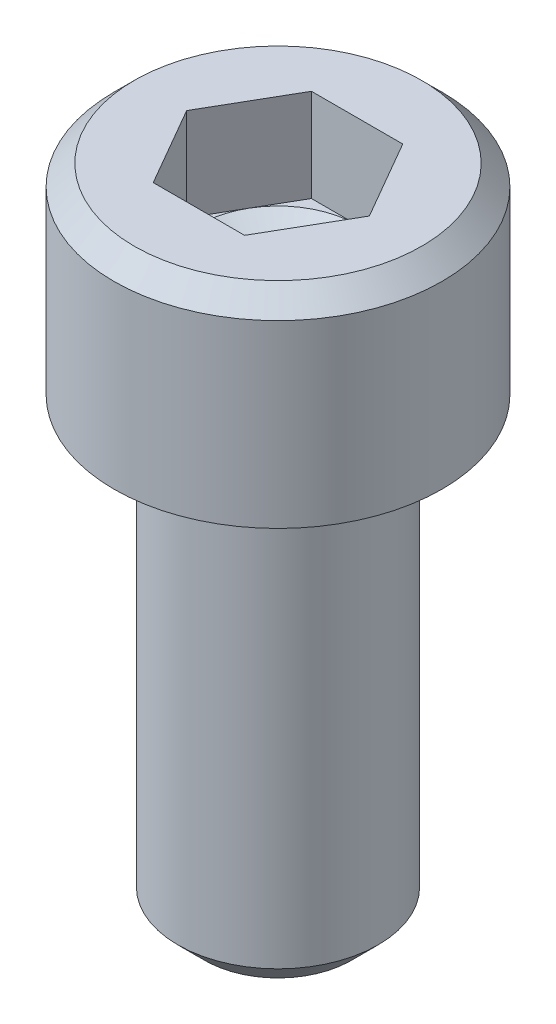
SolidWorks part; units mm, degrees
material "Alloy Steel"
ref_plane "Front Plane" through (0, 0, 0) normal (0, 0, 1) x (1, 0, 0)
ref_plane "Top Plane" through (0, 0, 0) normal (0, 1, 0) x (1, 0, 0)
ref_plane "Right Plane" through (0, 0, 0) normal (1, 0, 0) x (0, 0, -1)
sketch "Sketch1" plane through (0, 0, 0) normal (0, 0, 1) x (1, 0, 0)
  line L0 (2.8702, 3.5052) -> (0, 3.5052)
  line L1 (0, 3.5052) -> (0, 0)
  line L2 (0, 0) -> (2.8702, 0)
  line L3 (2.8702, 0) -> (2.8702, 3.5052)
  line L4 (0, 3.5052) -> (0, 0) construction
revolve "Revolve1" add sketch "Sketch1" angle 360 about L4 reverse direction yes
sketch "Sketch2" plane through (0, 0, 0) normal (0, -1, 0) x (1, 0, 0)
  circle A0 centre (0, 0) radius 1.7526
extrude "Boss-Extrude1" add sketch "Sketch2" along normal blind 7.9375
sketch "Sketch3" plane through (0, 3.5052, 0) normal (0, 1, 0) x (-1, 0, 0)
  line L0 (-0.7992, 1.3843) -> (-1.5985, 0)
  line L1 (-1.5985, 0) -> (-0.7992, -1.3843)
  line L2 (-0.7992, -1.3843) -> (0.7992, -1.3843)
  line L3 (0.7992, -1.3843) -> (1.5985, 0)
  line L4 (1.5985, 0) -> (0.7992, 1.3843)
  line L5 (0.7992, 1.3843) -> (-0.7992, 1.3843)
extrude "Cut-Extrude1" cut sketch "Sketch3" against normal blind 1.6256
sketch "Sketch4" plane through (0, 0, 0) normal (0, 0, 1) x (1, 0, 0)
  line L0 (1.3843, 1.8796) -> (0, 1.8796)
  line L1 (0, 1.8796) -> (0, 1.0804)
  line L2 (0, 1.0804) -> (1.3843, 1.8796)
  line L3 (0, 1.8796) -> (0, 1.0803) construction
revolve "Cut-Revolve1" cut sketch "Sketch4" angle 360 about L3 reverse direction yes
chamfer "Chamfer1" distance 0.4724 angle 45 1 edges at (0, -7.9375, -1.7526)
chamfer "Chamfer2" distance 0.3556 angle 45 1 edges at (0, 3.5052, -2.8702)
fillet "Fillet1" radius 0.254 1 edges at (0, 0, -1.7526) tangent propagation no
